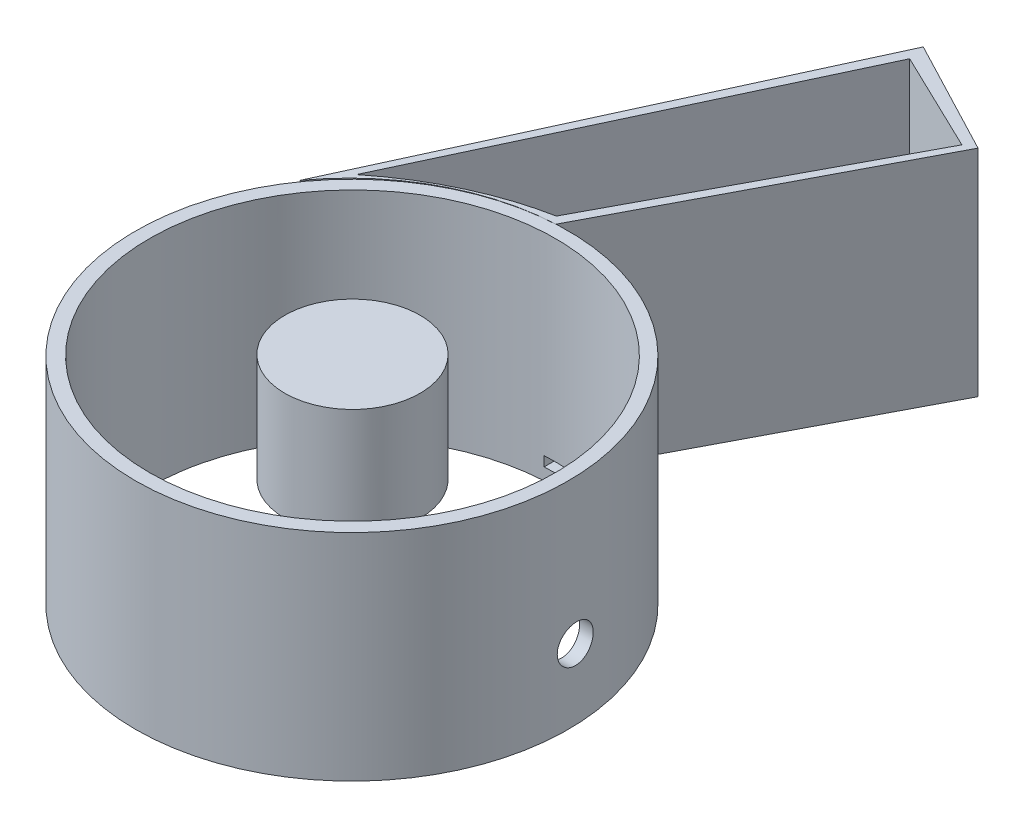
SolidWorks part; units mm, degrees
ref_plane "Front Plane" through (0, 0, 0) normal (0, 0, 1) x (1, 0, 0)
ref_plane "Top Plane" through (0, 0, 0) normal (0, 1, 0) x (1, 0, 0)
ref_plane "Right Plane" through (0, 0, 0) normal (1, 0, 0) x (0, 0, -1)
sketch "Sketch1" plane through (0, 0, 0) normal (0, 1, 0) x (1, 0, 0)
  circle A0 centre (-62.9348, -8.851) radius 40
  dimension "D1" = 80
extrude "Boss-Extrude2" add sketch "Sketch1" along normal blind 39.7893 contours A0
sketch "Sketch2" plane through (0, 39.7893, 0) normal (0, 1, 0) x (1, 0, 0)
  line L0 (-65.1657, 31.0868) -> (-38.3384, 82.2723)
  line L1 (-38.3384, 82.2723) -> (-59.5957, 93.4136)
  line L2 (-59.5957, 93.4136) -> (-95.8385, 14.4409)
  circle A0 centre (-62.9348, -8.851) radius 40 construction
  arc A4 (-65.1657, 31.0868) -> (-95.8385, 14.4409) centre (-63.2377, -9.0486) ccw
  dimension "D3" = 24
  dimension "D4" = 40.1817
  dimension "D1" = 86.8921
  dimension "D2" = 51.1856
extrude "Boss-Extrude3" add sketch "Sketch2" along normal blind 0.0001 and the other way blind 39.7911 separate body
sketch "Sketch6" plane through (0, 39.7893, 0) normal (0, 1, 0) x (1, 0, 0)
  line L2 (-63.0875, -49.7017) -> (-63.0265, -49.7017)
  circle A0 centre (-62.9348, -8.7452) radius 37.5
  dimension "D1" = 75
extrude "Cut-Extrude3" cut sketch "Sketch6" against normal through all contours A0 region at (-62.9348, 39.7893, 8.7452)
sketch "Sketch9" plane through (0, 39.7894, 0) normal (0, 1, 0) x (1, 0, 0)
  line L3 (-58.9594, 90.2637) -> (-40.3485, 81.302)
  line L4 (-40.3485, 81.302) -> (-66.4269, 32.4138)
  line L5 (-58.9594, 90.2637) -> (-91.5435, 20.5949)
  spline S0 degree 3 poles (-66.4269, 32.4138) (-75.6406, 30.6705) (-84.2488, 26.4275) (-91.5435, 20.5949) knots 0 0 0 0 1 1 1 1
  point P2 (-58.6778, 89.8883)
  point P5 (0, 0)
  point P6 (-58.9594, 90.2637)
extrude "Cut-Extrude4" cut sketch "Sketch9" against normal through all
sketch "Sketch10" plane through (0, 0, 0) normal (0, 1, 0) x (1, 0, 0)
  circle A0 centre (-62.9348, -8.745) radius 12.5
  dimension "D1" = 25
extrude "Boss-Extrude5" add sketch "Sketch10" along normal blind 40 and the other way blind 0.0001 separate body
sketch "Sketch11" plane through (0, 0, 0) normal (0, 1, 0) x (1, 0, 0)
  circle A0 centre (-84.9007, 18.0352) radius 2.75
  circle A2 centre (-41.7961, 18.7978) radius 2.75
  circle A3 centre (-84.807, -35.7126) radius 2.75
  circle A4 centre (-41.4039, -35.9936) radius 2.75
  circle A5 centre (-59.0289, 83.524) radius 2.75
  circle A6 centre (-67.3311, 36.9389) radius 2.75
  point P6 (-58.7952, 83.4461)
  point P13 (-59.0289, 83.524)
  dimension "D1" = 5.5
  dimension "D2" = 5.5
  dimension "D3" = 5.5
  dimension "D4" = 5.5
  dimension "D5" = 5.5
  dimension "D6" = 5.5
extrude "Boss-Extrude6" add sketch "Sketch11" along normal blind 4.02
sketch "Sketch12" plane through (0, 4.02, 0) normal (0, 1, 0) x (1, 0, 0)
  circle A0 centre (-84.9007, 18.0352) radius 2.225
  circle A1 centre (-84.807, -35.7126) radius 2.225
  circle A2 centre (-41.7961, 18.7978) radius 2.225
  circle A3 centre (-41.4039, -35.9936) radius 2.225
  circle A4 centre (-67.3311, 36.9389) radius 2.225
  circle A5 centre (-59.0289, 83.524) radius 2.225
  point P18 (-55.2897, 82.6035)
  dimension "D1" = 4.45
  dimension "D2" = 4.45
  dimension "D3" = 4.45
  dimension "D4" = 4.45
  dimension "D5" = 4.45
  dimension "D6" = 4.45
extrude "Cut-Extrude5" cut sketch "Sketch12" against normal through all
sketch "Sketch15" plane through (0, -0.0001, 0) normal (0, -1, 0) x (1, 0, 0)
  circle A0 centre (-62.9348, 8.745) radius 12.5
extrude "Cut-Extrude6" cut sketch "Sketch15" against normal blind 20
sketch "Sketch20" plane through (0, 0, 0) normal (1, 0, 0) x (0, 0, -1)
  circle A0 centre (-7.4026, 12.9879) radius 3.45
  dimension "D1" = 6.9
extrude "Cut-Extrude15" cut sketch "Sketch20" against normal blind 34
sketch "Sketch21" plane through (0, 0, 0) normal (0, 0, 1) x (1, 0, 0)
  line L0 (-58.1046, 4.0382) -> (-58.1046, 2.2382)
  line L1 (-58.1046, 2.2382) -> (-64.9546, 2.2382)
  line L2 (-64.9546, 2.2382) -> (-64.9546, 4.0382)
  line L3 (-64.9546, 4.0382) -> (-58.1046, 4.0382)
  dimension "D1" = 1.8
  dimension "D2" = 6.85
extrude "Cut-Extrude17" cut sketch "Sketch21" against normal blind 34 contours L3 L0 L1 L2
extrude "Cut-Extrude18" cut sketch "Sketch12<2>" against normal blind 34
sketch "Sketch12<2>" plane through (0, 4.02, 0) normal (0, 1, 0) x (1, 0, 0) same geometry as "Sketch12"
